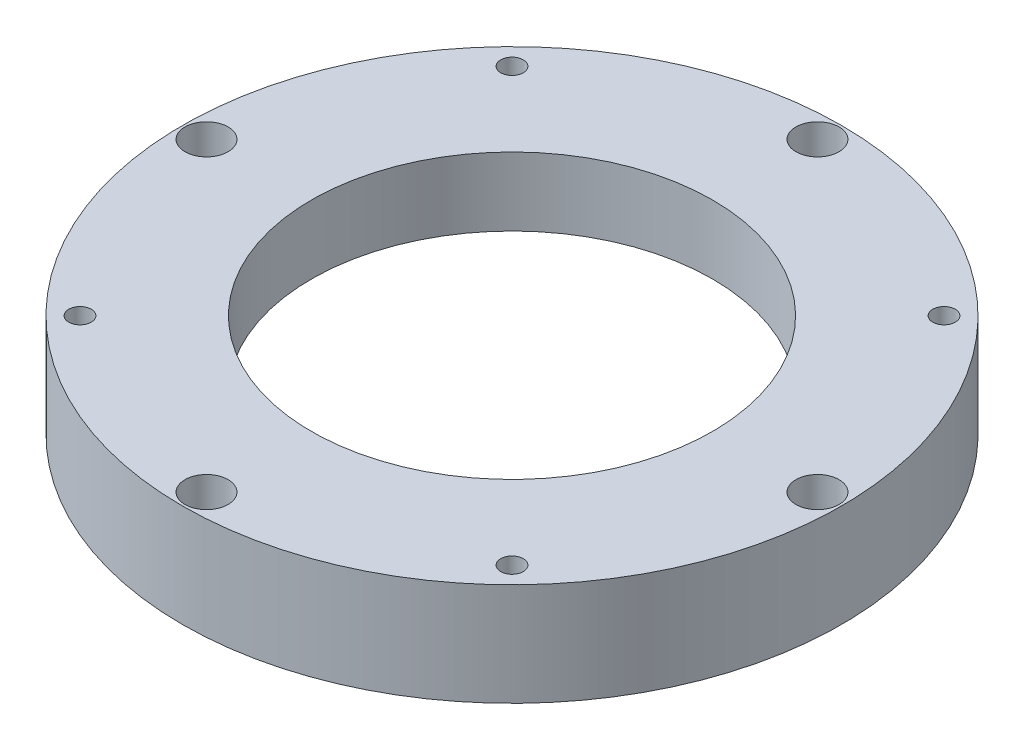
SolidWorks part; units mm, degrees
ref_plane "Front Plane" through (0, 0, 0) normal (0, 0, 1) x (1, 0, 0)
ref_plane "Top Plane" through (0, 0, 0) normal (0, 1, 0) x (1, 0, 0)
ref_plane "Right Plane" through (0, 0, 0) normal (1, 0, 0) x (0, 0, -1)
sketch "Sketch1" plane through (0, 0, 0) normal (0, 1, 0) x (1, 0, 0)
  line L0 (0, 0) -> (42.5, 0) construction
  circle A0 centre (0, 0) radius 45.85
  circle A1 centre (0, 0) radius 27.9
  circle A2 centre (42.5, 0) radius 1.5635
  circle A3 centre (30.052, -30.052) radius 1.5635
  circle A4 centre (0, -42.5) radius 1.5635
  circle A5 centre (0, 0) radius 40.5
  circle A6 centre (-30.052, -30.052) radius 1.5635
  circle A7 centre (-42.5, 0) radius 1.5635
  circle A8 centre (-30.052, 30.052) radius 1.5635
  circle A9 centre (0, 42.5) radius 1.5635
  circle A10 centre (30.052, 30.052) radius 1.5635
  point P13 (0, 0)
  dimension "D1" = 91.7
  dimension "D2" = 55.8
  dimension "D4" = 3.127
  dimension "D6" = 81
  dimension "D3" = 42.5
  dimension "D5" = 8
extrude "Boss-Extrude1" add sketch "Sketch1" against normal blind 4.7625 contours A0 A5 A2 A4 A3 region at (-44.5532, 0, 0)
extrude "Boss-Extrude2" add sketch "Sketch1<4>" along normal blind 4.7625 contours A1 A5 | A0 A5 A2 A4 A3 region at (-44.5532, 0, 0) region at (-39.3545, 0, 0)
sketch "Sketch1<4>" plane through (0, 0, 0) normal (0, 1, 0) x (1, 0, 0) same geometry as "Sketch1"
sketch "Sketch4" plane through (0, 4.7625, 0) normal (0, 1, 0) x (1, 0, 0)
  line L0 (28.4932, -27.352) -> (26.9343, -30.052)
  line L7 (30.052, 33.1697) -> (27.352, 31.6109)
  line L8 (27.352, 31.6109) -> (27.352, 28.4932)
  line L9 (27.352, 28.4932) -> (30.052, 26.9343)
  line L10 (30.052, 26.9343) -> (32.752, 28.4932)
  line L11 (32.752, 28.4932) -> (32.752, 31.6109)
  line L12 (32.752, 31.6109) -> (30.052, 33.1697)
  line L13 (31.6109, -27.352) -> (28.4932, -27.352)
  line L14 (33.1697, -30.052) -> (31.6109, -27.352)
  line L15 (31.6109, -32.752) -> (33.1697, -30.052)
  line L16 (28.4932, -32.752) -> (31.6109, -32.752)
  line L17 (26.9343, -30.052) -> (28.4932, -32.752)
  line L18 (-27.352, -28.4932) -> (-30.052, -26.9343)
  line L19 (-27.352, -31.6109) -> (-27.352, -28.4932)
  line L20 (-30.052, -33.1697) -> (-27.352, -31.6109)
  line L21 (-32.752, -31.6109) -> (-30.052, -33.1697)
  line L22 (-32.752, -28.4932) -> (-32.752, -31.6109)
  line L23 (-30.052, -26.9343) -> (-32.752, -28.4932)
  line L24 (-28.4932, 27.352) -> (-26.9343, 30.052)
  line L25 (-31.6109, 27.352) -> (-28.4932, 27.352)
  line L26 (-33.1697, 30.052) -> (-31.6109, 27.352)
  line L27 (-31.6109, 32.752) -> (-33.1697, 30.052)
  line L28 (-28.4932, 32.752) -> (-31.6109, 32.752)
  line L29 (-26.9343, 30.052) -> (-28.4932, 32.752)
  circle A0 centre (30.052, 30.052) radius 2.7 construction
  point P1 (31.402, 32.3903)
  point P32 (0, 0)
  dimension "D1" = 5.4
  dimension "D2" = 4
extrude "Cut-Extrude2" cut sketch "Sketch4" against normal blind 4.7625
sketch "Sketch3" plane through (0, 4.7625, 0) normal (0, 1, 0) x (1, 0, 0)
  circle A6 centre (0, -42.5) radius 1.5635 construction
  circle A7 centre (42.5, 0) radius 1.5635 construction
  circle A8 centre (0, 42.5) radius 1.5635 construction
  circle A9 centre (-42.5, 0) radius 1.5635 construction
  circle A10 centre (0, 0) radius 27.9 construction
  circle A11 centre (0, 0) radius 45.85 construction
  circle A12 centre (0, -42.5) radius 1.5635
  circle A13 centre (42.5, 0) radius 1.5635
  circle A14 centre (0, 42.5) radius 1.5635
  circle A15 centre (-42.5, 0) radius 1.5635
  circle A16 centre (0, 0) radius 27.9
  circle A17 centre (0, 0) radius 45.85
  circle A18 centre (0, 42.5) radius 3
  circle A19 centre (42.5, 0) radius 3
  circle A20 centre (0, -42.5) radius 3
  circle A21 centre (-42.5, 0) radius 3
  circle A22 centre (-30.052, 30.052) radius 1.565
  circle A23 centre (30.052, 30.052) radius 1.565
  circle A24 centre (30.052, -30.052) radius 1.565
  circle A25 centre (-30.052, -30.052) radius 1.565
  circle M1 centre (0, 0) radius 27.9
  circle M6 centre (0, 0) radius 45.85
  line M21 (-33.1697, 30.052) -> (-31.6109, 32.752)
  line M22 (-31.6109, 32.752) -> (-28.4932, 32.752)
  line M23 (-28.4932, 32.752) -> (-26.9343, 30.052)
  line M24 (-26.9343, 30.052) -> (-28.4932, 27.352)
  line M25 (-28.4932, 27.352) -> (-31.6109, 27.352)
  line M26 (-31.6109, 27.352) -> (-33.1697, 30.052)
  line M27 (-30.052, -33.1697) -> (-32.752, -31.6109)
  line M28 (-32.752, -31.6109) -> (-32.752, -28.4932)
  line M29 (-32.752, -28.4932) -> (-30.052, -26.9343)
  line M30 (-30.052, -26.9343) -> (-27.352, -28.4932)
  line M31 (-27.352, -28.4932) -> (-27.352, -31.6109)
  line M32 (-27.352, -31.6109) -> (-30.052, -33.1697)
  line M33 (33.1697, -30.052) -> (31.6109, -32.752)
  line M34 (31.6109, -32.752) -> (28.4932, -32.752)
  line M35 (28.4932, -32.752) -> (26.9343, -30.052)
  line M36 (26.9343, -30.052) -> (28.4932, -27.352)
  line M37 (28.4932, -27.352) -> (31.6109, -27.352)
  line M38 (31.6109, -27.352) -> (33.1697, -30.052)
  line M39 (30.052, 33.1697) -> (32.752, 31.6109)
  line M40 (32.752, 31.6109) -> (32.752, 28.4932)
  line M41 (32.752, 28.4932) -> (30.052, 26.9343)
  line M42 (30.052, 26.9343) -> (27.352, 28.4932)
  line M43 (27.352, 28.4932) -> (27.352, 31.6109)
  line M44 (27.352, 31.6109) -> (30.052, 33.1697)
  dimension "D1" = 6
  dimension "D2" = 3.13
extrude "Boss-Extrude3" add sketch "Sketch3" along normal blind 4.7625 contours A21 A20 A19 A18 M6 M1 M44 M39 M40 M41 M42 M43 M38 M33 M34 M35 M36 M37 M32 M27 M28 M29 M30 M31 M26 M21 M22 M23 M24 M25 | A22 M21 M26 M25 M24 M23 M22 | A23 M39 M44 M43 M42 M41 M40 | A24 M33 M38 M37 M36 M35 M34 | A25 M27 M32 M31 M30 M29 M28 region at (-45.7203, 4.7625, 0) region at (-32.3189, 4.7625, -31.3608) region at (-31.3608, 4.7625, 32.3189) region at (32.3189, 4.7625, 31.3608) region at (31.3608, 4.7625, -32.3189)
sketch "Sketch5" plane through (0, 9.525, 0) normal (0, 1, 0) x (1, 0, 0)
  line L0 (0, 0) -> (30.052, 30.052) construction
  circle A0 centre (0, 42.5) radius 3 construction
  circle A1 centre (30.052, 30.052) radius 1.565 construction
  circle A2 centre (42.5, 0) radius 3 construction
  circle A3 centre (30.052, -30.052) radius 1.565 construction
  circle A4 centre (0, -42.5) radius 3 construction
  circle A5 centre (-30.052, -30.052) radius 1.565 construction
  circle A6 centre (-42.5, 0) radius 3 construction
  circle A7 centre (-30.052, 30.052) radius 1.565 construction
  circle A8 centre (0, 0) radius 45.85 construction
  circle A9 centre (0, 0) radius 27.9 construction
  circle A10 centre (0, 42.5) radius 3
  circle A11 centre (30.052, 30.052) radius 1.565
  circle A12 centre (42.5, 0) radius 3
  circle A13 centre (30.052, -30.052) radius 1.565
  circle A14 centre (0, -42.5) radius 3
  circle A15 centre (-30.052, -30.052) radius 1.565
  circle A16 centre (-42.5, 0) radius 3
  circle A17 centre (-30.052, 30.052) radius 1.565
  circle A18 centre (0, 0) radius 45.85
  circle A19 centre (0, 0) radius 27.9
  arc A20 (6.31, 31.2697) -> (18.4511, 26.0224) centre (0, 0) cw
  arc A21 (4.6718, 37.2871) -> (6.4423, 39.762) centre (0, 42.5) ccw
  arc A22 (24.5734, 31.0284) -> (24.5119, 29.527) centre (30.052, 30.052) ccw
  arc A23 (24.5119, 29.527) -> (18.4511, 26.0224) centre (20.6784, 29.1636) cw
  arc A24 (4.6718, 37.2871) -> (6.31, 31.2697) centre (7, 34.6892) ccw
  arc A25 (22.8162, 35.0834) -> (24.5734, 31.0284) centre (20.6354, 31.7302) cw
  arc A26 (8.6987, 40.936) -> (6.4423, 39.762) centre (8.283, 38.9797) ccw
  arc A27 (22.8162, 35.0834) -> (8.6987, 40.936) centre (0, 0) ccw
  arc A28 (35.0834, 22.8162) -> (31.0284, 24.5734) centre (31.7302, 20.6354) ccw
  arc A29 (31.0284, 24.5734) -> (29.527, 24.5119) centre (30.052, 30.052) cw
  arc A30 (29.527, 24.5119) -> (26.0224, 18.4511) centre (29.1636, 20.6784) ccw
  arc A31 (31.2697, 6.31) -> (26.0224, 18.4511) centre (0, 0) ccw
  arc A32 (35.0834, 22.8162) -> (40.936, 8.6987) centre (0, 0) cw
  arc A33 (40.936, 8.6987) -> (39.762, 6.4423) centre (38.9797, 8.283) cw
  arc A34 (37.2871, 4.6718) -> (39.762, 6.4423) centre (42.5, 0) cw
  arc A35 (37.2871, 4.6718) -> (31.2697, 6.31) centre (34.6892, 7) cw
  arc A36 (37.2871, -4.6718) -> (31.2697, -6.31) centre (34.6892, -7) ccw
  arc A37 (31.2697, -6.31) -> (26.0224, -18.4511) centre (0, 0) cw
  arc A38 (29.527, -24.5119) -> (26.0224, -18.4511) centre (29.1636, -20.6784) cw
  arc A39 (31.0284, -24.5734) -> (29.527, -24.5119) centre (30.052, -30.052) ccw
  arc A40 (35.0834, -22.8162) -> (31.0284, -24.5734) centre (31.7302, -20.6354) cw
  arc A41 (35.0834, -22.8162) -> (40.936, -8.6987) centre (0, 0) ccw
  arc A42 (40.936, -8.6987) -> (39.762, -6.4423) centre (38.9797, -8.283) ccw
  arc A43 (37.2871, -4.6718) -> (39.762, -6.4423) centre (42.5, 0) ccw
  arc A44 (24.5119, -29.527) -> (18.4511, -26.0224) centre (20.6784, -29.1636) ccw
  arc A45 (24.5734, -31.0284) -> (24.5119, -29.527) centre (30.052, -30.052) cw
  arc A46 (22.8162, -35.0834) -> (24.5734, -31.0284) centre (20.6354, -31.7302) ccw
  arc A47 (22.8162, -35.0834) -> (8.6987, -40.936) centre (0, 0) cw
  arc A48 (6.31, -31.2697) -> (18.4511, -26.0224) centre (0, 0) ccw
  arc A49 (4.6718, -37.2871) -> (6.31, -31.2697) centre (7, -34.6892) cw
  arc A50 (4.6718, -37.2871) -> (6.4423, -39.762) centre (0, -42.5) cw
  arc A51 (8.6987, -40.936) -> (6.4423, -39.762) centre (8.283, -38.9797) cw
  arc A52 (-4.6718, -37.2871) -> (-6.31, -31.2697) centre (-7, -34.6892) ccw
  arc A53 (-6.31, -31.2697) -> (-18.4511, -26.0224) centre (0, 0) cw
  arc A54 (-24.5119, -29.527) -> (-18.4511, -26.0224) centre (-20.6784, -29.1636) cw
  arc A55 (-24.5734, -31.0284) -> (-24.5119, -29.527) centre (-30.052, -30.052) ccw
  arc A56 (-22.8162, -35.0834) -> (-24.5734, -31.0284) centre (-20.6354, -31.7302) cw
  arc A57 (-22.8162, -35.0834) -> (-8.6987, -40.936) centre (0, 0) ccw
  arc A58 (-8.6987, -40.936) -> (-6.4423, -39.762) centre (-8.283, -38.9797) ccw
  arc A59 (-4.6718, -37.2871) -> (-6.4423, -39.762) centre (0, -42.5) ccw
  arc A60 (-29.527, -24.5119) -> (-26.0224, -18.4511) centre (-29.1636, -20.6784) ccw
  arc A61 (-31.0284, -24.5734) -> (-29.527, -24.5119) centre (-30.052, -30.052) cw
  arc A62 (-35.0834, -22.8162) -> (-31.0284, -24.5734) centre (-31.7302, -20.6354) ccw
  arc A63 (-35.0834, -22.8162) -> (-40.936, -8.6987) centre (0, 0) cw
  arc A64 (-31.2697, -6.31) -> (-26.0224, -18.4511) centre (0, 0) ccw
  arc A65 (-37.2871, -4.6718) -> (-31.2697, -6.31) centre (-34.6892, -7) cw
  arc A66 (-37.2871, -4.6718) -> (-39.762, -6.4423) centre (-42.5, 0) cw
  arc A67 (-40.936, -8.6987) -> (-39.762, -6.4423) centre (-38.9797, -8.283) cw
  arc A68 (-37.2871, 4.6718) -> (-31.2697, 6.31) centre (-34.6892, 7) ccw
  arc A69 (-31.2697, 6.31) -> (-26.0224, 18.4511) centre (0, 0) cw
  arc A70 (-29.527, 24.5119) -> (-26.0224, 18.4511) centre (-29.1636, 20.6784) cw
  arc A71 (-31.0284, 24.5734) -> (-29.527, 24.5119) centre (-30.052, 30.052) ccw
  arc A72 (-35.0834, 22.8162) -> (-31.0284, 24.5734) centre (-31.7302, 20.6354) cw
  arc A73 (-35.0834, 22.8162) -> (-40.936, 8.6987) centre (0, 0) ccw
  arc A74 (-40.936, 8.6987) -> (-39.762, 6.4423) centre (-38.9797, 8.283) ccw
  arc A75 (-37.2871, 4.6718) -> (-39.762, 6.4423) centre (-42.5, 0) ccw
  arc A76 (-24.5119, 29.527) -> (-18.4511, 26.0224) centre (-20.6784, 29.1636) ccw
  arc A77 (-24.5734, 31.0284) -> (-24.5119, 29.527) centre (-30.052, 30.052) cw
  arc A78 (-22.8162, 35.0834) -> (-24.5734, 31.0284) centre (-20.6354, 31.7302) ccw
  arc A79 (-22.8162, 35.0834) -> (-8.6987, 40.936) centre (0, 0) cw
  arc A80 (-6.31, 31.2697) -> (-18.4511, 26.0224) centre (0, 0) ccw
  arc A81 (-4.6718, 37.2871) -> (-6.31, 31.2697) centre (-7, 34.6892) cw
  arc A82 (-4.6718, 37.2871) -> (-6.4423, 39.762) centre (0, 42.5) cw
  arc A83 (-8.6987, 40.936) -> (-6.4423, 39.762) centre (-8.283, 38.9797) cw
  point P137 (0, 0)
  dimension "D1" = 4
  dimension "D2" = 4
  dimension "D3" = 4
  dimension "D4" = 4
  dimension "D5" = 12
  dimension "D8" = 2
  dimension "D9" = 4
  dimension "D7" = 14
  dimension "D6" = 4
extrude "Cut-Extrude3" [suppressed] cut sketch "Sketch5" against normal blind 4.7625 contours A75 A68 A69 A70 A71 A72 A73 A74 | A83 A79 A78 A77 A76 A80 A81 A82 | A25 A27 A26 A21 A24 A20 A23 A22 | A35 A34 A33 A32 A28 A29 A30 A31 | A43 A36 A37 A38 A39 A40 A41 A42 | A51 A47 A46 A45 A44 A48 A49 A50 | A59 A52 A53 A54 A55 A56 A57 A58 | A67 A63 A62 A61 A60 A64 A65 A66
equation "\"bearing_21_OD\"= 21mm"
equation "\"pin_cirlce_diameter\"= 75mm"
equation "\"pin_diam\"= 6mm"
equation "\"gear_thickness\"= 4mm"
equation "\"ball_bearing_diam\"= 3.214mm"
equation "\"bearing_21_outer_clearance\"= 0.127mm'change this"
equation "\"bearing_15_OD\"= 15mm"
equation "\"bearing_15_outer_clearance\"= 0mm'change this"
equation "\"thrust_bearing_thickness\"= 5mm'measure this irl and change"
equation "\"D1@Boss-Extrude1\"=\"sheetThickness\""
equation "\"largeBearOD\"= 21mm"
equation "\"largeBearID\"= 15mm"
equation "\"largeBearOTight\"= 0.34375mm'calibrate - hold onto gears"
equation "\"largeBearITight\"= 0mm'calibrate - hold onto eccentric nut"
equation "\"largeBearFlangeDiam\"= 22.5mm"
equation "\"largeBearFlangeWidth\"= 0.8mm"
equation "\"smallBearOD\"= 14.8mm"
equation "\"smallBearOTight\"= 0mm'calibrate - hold onto bottom of gearbox"
equation "\"smallBearOLoose\"= 0mm'calibrate - able to take off topHat"
equation "\"smallBearID\"= 10mm"
equation "\"smallBearITight\"= 0mm'hold onto "
equation "\"pinCircleDiam\"= 75mm"
equation "\"pinDiam\"= 6mm"
equation "\"sheetThickness\"= 0.1875in"
equation "\"ballBearDiam\"= 3.5mm"
equation "\"thrustBearingThickness\"= 5mm'measure this irl and change"
equation "\"thrustBearingID\"= 0mm'measure this irl and change"
equation "\"thrustBearingOD\"= 0mm'measure this irl and change"
equation "\"eccentricity\"= 1mm"
equation "\"D1@Boss-Extrude2\"=\"sheetThickness\""
equation "\"D1@Boss-Extrude3\"=\"sheetThickness\""
equation "\"D1@Cut-Extrude2\"=\"sheetThickness\""
equation "\"D1@Cut-Extrude3\"=\"sheetThickness\""
